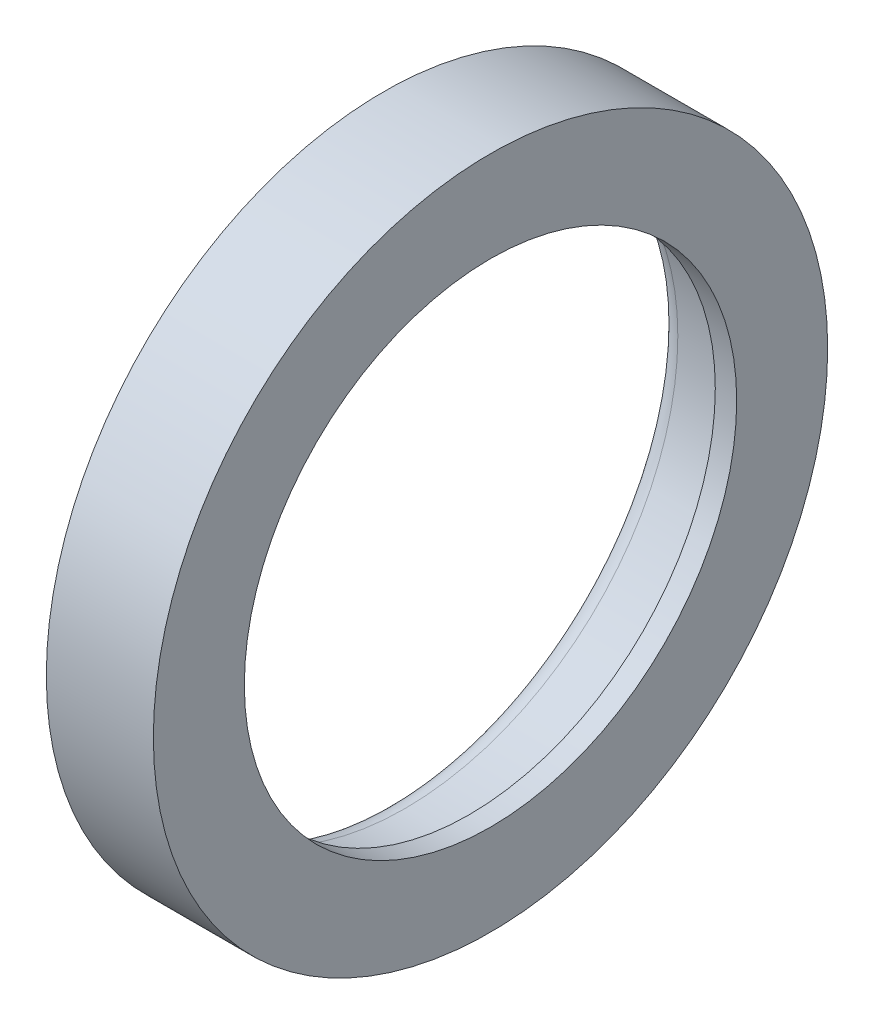
SolidWorks part; units mm, degrees
ref_plane "Front Plane" through (0, 0, 0) normal (0, 0, 1) x (1, 0, 0)
ref_plane "Top Plane" through (0, 0, 0) normal (0, 1, 0) x (1, 0, 0)
ref_plane "Right Plane" through (0, 0, 0) normal (1, 0, 0) x (0, 0, -1)
sketch "Sketch1" plane through (0, 0, 0) normal (1, 0, 0) x (0, 0, -1)
  line L0 (12.75, 0) -> (15.75, 0)
  line L1 (12.75, 0) -> (12.5, 0)
  line L2 (12.5, 0) -> (11.5, 0) construction
  circle A0 centre (0, 0) radius 12.5 construction
  circle A1 centre (0, 0) radius 12.75
  circle A2 centre (0, 0) radius 15.75
  circle A4 centre (0, 0) radius 12.5 construction
  circle A5 centre (0, 0) radius 11.5
  dimension "D3" = 1
  dimension "D1" = 3
  dimension "D2" = 0.25
extrude "Boss-Extrude1" add sketch "Sketch1" against normal blind 5 contours A2 A1 region at (0, 0, 15.3045)
sketch "Sketch2" plane through (0, 0, 0) normal (1, 0, 0) x (0, 0, -1)
  line L0 (0, -15.75) -> (0, -35) construction
  line L5 (-2.5, -35) -> (2.5, -35)
  line L6 (2.5, -35) -> (2.5, -15.5503)
  line L7 (-2.5, -35) -> (-2.5, -15.5503)
  line L8 (2.5, -25.2752) -> (-2.5, -25.2752) construction
  line L9 (-2.5, -15.5503) -> (2.5, -15.5503)
  circle A0 centre (0, 0) radius 15.75 construction
  circle A1 centre (0, 0) radius 15.75 construction
  point P10 (0, -35)
  dimension "D1" = 5
fillet "Fillet3" radius 1 1 edges at (-5, 0, -12.75)
extrude "Boss-Extrude29" add sketch "Sketch1<3>" against normal blind 1 contours A1 A5 region at (0, 0, 12.3894)
sketch "Sketch1<3>" plane through (0, 0, 0) normal (1, 0, 0) x (0, 0, -1) same geometry as "Sketch1"
